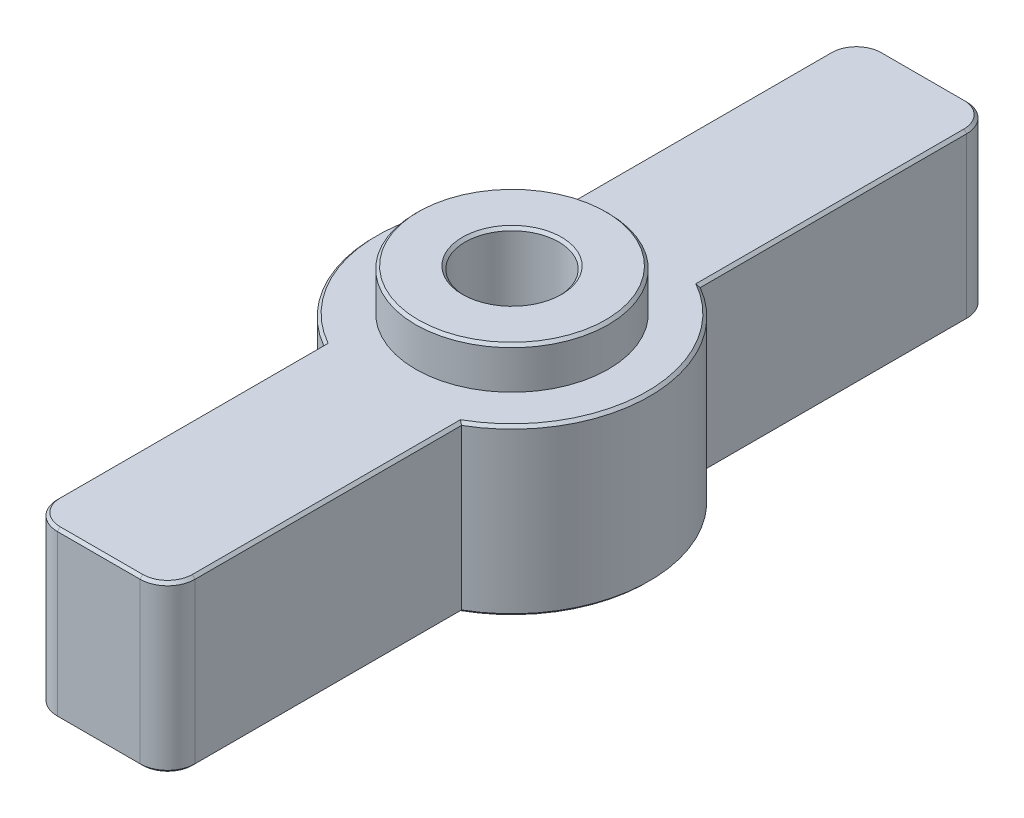
SolidWorks part; units mm, degrees
ref_plane "Front Plane" through (0, 0, 0) normal (0, 0, 1) x (1, 0, 0)
ref_plane "Top Plane" through (0, 0, 0) normal (0, 1, 0) x (1, 0, 0)
ref_plane "Right Plane" through (0, 0, 0) normal (1, 0, 0) x (0, 0, -1)
other "Configuration Table"
sketch "草图1" plane through (0, 0, 0) normal (0, 1, 0) x (1, 0, 0)
  line L0 (-5, 0) -> (5, 0) construction
  line L1 (-5, -28) -> (-5, -8.6603)
  line L2 (5, -28) -> (5, -8.6603)
  line L3 (-3, 30) -> (3, 30)
  line L4 (-3, -30) -> (3, -30)
  line L5 (-5, 8.6603) -> (-5, 28)
  line L6 (5, 8.6603) -> (5, 28)
  arc A0 (-5, 8.6603) -> (-5, -8.6603) centre (0, 0) ccw
  arc A1 (3, -30) -> (5, -28) centre (3, -28) ccw
  arc A2 (-3, -30) -> (-5, -28) centre (-3, -28) cw
  arc A3 (5, 28) -> (3, 30) centre (3, 28) ccw
  arc A4 (-5, 28) -> (-3, 30) centre (-3, 28) cw
  arc A5 (5, -8.6603) -> (5, 8.6603) centre (0, 0) ccw
  point P6 (0, 0)
  point P9 (-5, 0)
  point P12 (5, 0)
  dimension "D1" = 60
  dimension "D2" = 2
  dimension "D3" = 10
extrude "凸台-拉伸1" add sketch "草图1" along normal blind 12
sketch "草图2" plane through (0, 0, 0) normal (0, -1, 0) x (1, 0, 0)
  circle A0 centre (0, 0) radius 6.75
extrude "切除-拉伸1" cut sketch "草图2" against normal blind 8.5
sketch "草图4" plane through (0, 12, 0) normal (0, 1, 0) x (1, 0, 0)
  circle A0 centre (0, 0) radius 7
  dimension "D1" = 14
extrude "凸台-拉伸2" add sketch "草图4" along normal blind 3
sketch "草图3" plane through (0, 8.5, 0) normal (0, -1, 0) x (1, 0, 0)
  circle A0 centre (0, 0) radius 3.4
  dimension "D1" = 6.8
extrude "切除-拉伸2" cut sketch "草图3" against normal through all
chamfer "倒角1" distance 0.2 angle 45 27 edges at (5, 12, 18.3301) (4.4142, 12, 29.4142) (0, 12, 30) (-4.4142, 12, 29.4142) (-5, 12, 18.3301) (0, 15, 7) (0, 15, -3.4) (5, 0, -18.3301) (4.4142, 0, -29.4142) (0, 0, -30) (-4.4142, 0, -29.4142) (-5, 0, -18.3301) (-5, 0, 18.3301) (-4.4142, 0, 29.4142) (0, 0, 30) (4.4142, 0, 29.4142) (5, 0, 18.3301) (-10, 0, 0) (0, 0, -6.75) (-5, 12, -18.3301) (-4.4142, 12, -29.4142) (0, 12, -30) (4.4142, 12, -29.4142) (5, 12, -18.3301) (-10, 12, 0) (10, 12, 0) (10, 0, 0)
